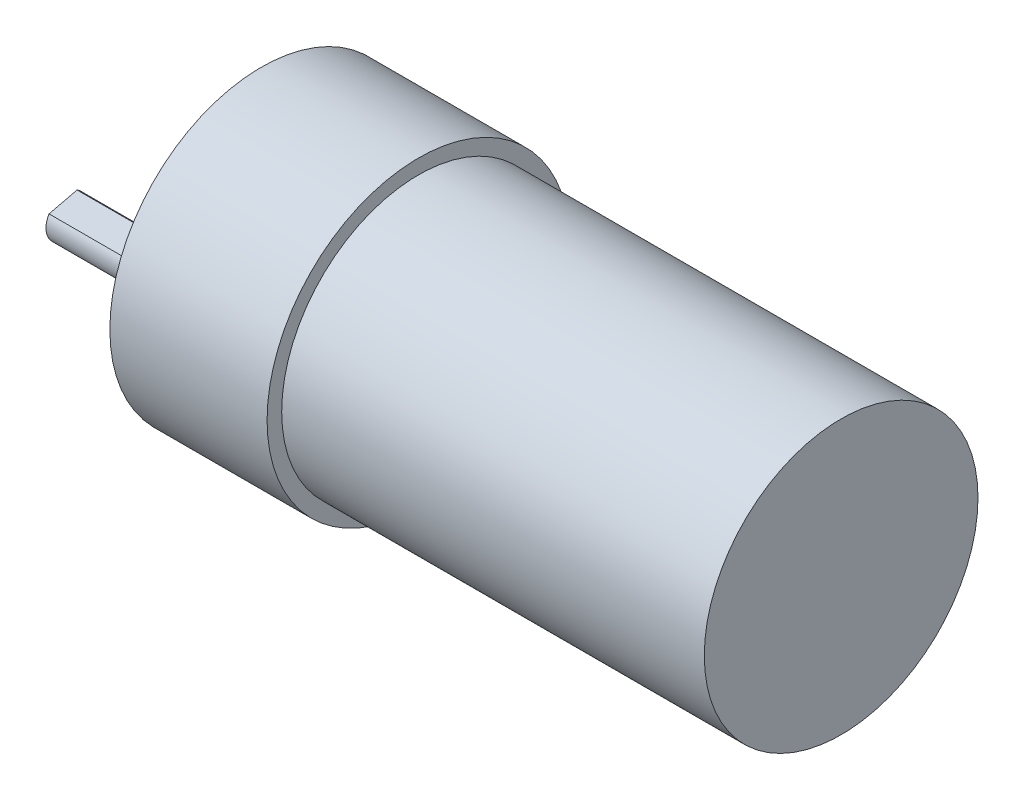
SolidWorks part; units mm, degrees
material "Steel Shell"
ref_plane "Front Plane" through (0, 0, 0) normal (0, 0, 1) x (1, 0, 0)
ref_plane "Top Plane" through (0, 0, 0) normal (0, 1, 0) x (1, 0, 0)
ref_plane "Right Plane" through (0, 0, 0) normal (1, 0, 0) x (0, 0, -1)
sketch "Sketch1" plane through (0, 0, 0) normal (1, 0, 0) x (0, 0, -1)
  circle A0 centre (0, 0) radius 15.875
  dimension "D1" = 31.75
extrude "Extrude1" add sketch "Sketch1" along normal blind 49.022
sketch "Sketch3" plane through (0, 0, 0) normal (-1, 0, 0) x (0, 0, 1)
  circle A0 centre (0, 0) radius 17.5692
extrude "Extrude3" add sketch "Sketch3" along normal blind 18.2372
sketch "Sketch4" plane through (-18.2372, 0, 0) normal (-1, 0, 0) x (0, 0, 1)
  line L0 (0, 0) -> (0, -8.7186) construction
  circle A0 centre (0, -8.7186) radius 2.3749
  dimension "D2" = 4.7498
  dimension "D1" = 8.7186
extrude "Extrude4" add sketch "Sketch4" along normal blind 22.606
sketch "Sketch5" plane through (-18.2372, 0, 0) normal (-1, 0, 0) x (0, 0, 1)
  line L0 (0, 17.5692) -> (0, 13.4556) construction
  circle A0 centre (0, 0) radius 17.5692 construction
  circle A1 centre (0, 13.4556) radius 1.27
  circle A3 centre (0, -8.7186) radius 2.3749 construction
  dimension "D2" = 2.54
  dimension "D1" = 22.1742
extrude "Cut-Extrude1" cut sketch "Sketch5" against normal blind 10
sketch "Sketch6" plane through (-18.2372, 0, 0) normal (-1, 0, 0) x (0, 0, 1)
  line L0 (0, -8.7186) -> (10.2108, -8.7186) construction
  line L1 (0, -8.7186) -> (-10.2108, -8.7186) construction
  circle A0 centre (10.2108, -8.7186) radius 1.27
  circle A4 centre (0, 13.4556) radius 1.27 construction
  circle A5 centre (-10.2108, -8.7186) radius 1.27
  circle A6 centre (0, 13.4556) radius 1.27 construction
  dimension "D1" = 10.2108
extrude "Cut-Extrude2" cut sketch "Sketch6" against normal blind 10
sketch3d "3DSketch3"
  circle A0 centre (-18.2372, -8.7186, 10.2108) radius 1.27 construction
  point P2 (-19.5072, -8.7186, 10.2108)
sketch "Sketch7" plane through (0, -5.9371, -1.4198) normal (0, 0.9726, 0.2326) x (-1, 0, 0)
  line L0 (25.8572, 1.8493) -> (18.2372, 1.8493) construction
  line L1 (25.8572, 6.9456) -> (43.5843, 6.9456)
  line L2 (25.8572, 6.9456) -> (25.8572, -4.0683)
  line L3 (25.8572, -4.0683) -> (43.5843, -4.0683)
  line L4 (43.5843, 6.9456) -> (43.5843, -4.0683)
  line L5 (18.2372, -0.3471) -> (18.2372, 4.4027) construction
  dimension "D1" = 7.62
extrude "Cut-Extrude3" cut sketch "Sketch7" against normal blind 0.6858
sketch "Sketch9" plane through (0, 0, 0) normal (1, 0, 0) x (0, 0, -1)
  line L0 (0, 0) -> (0, 15.875)
  circle A0 centre (0, 0) radius 15.875 construction
ref_plane "Plane3" through (0, 15.875, 0) normal (0, 1, 0) x (-1, 0, 0)
ref_plane "Plane4" through (0, -17.5692, 0) normal (0, -1, 0) x (-1, 0, 0)
